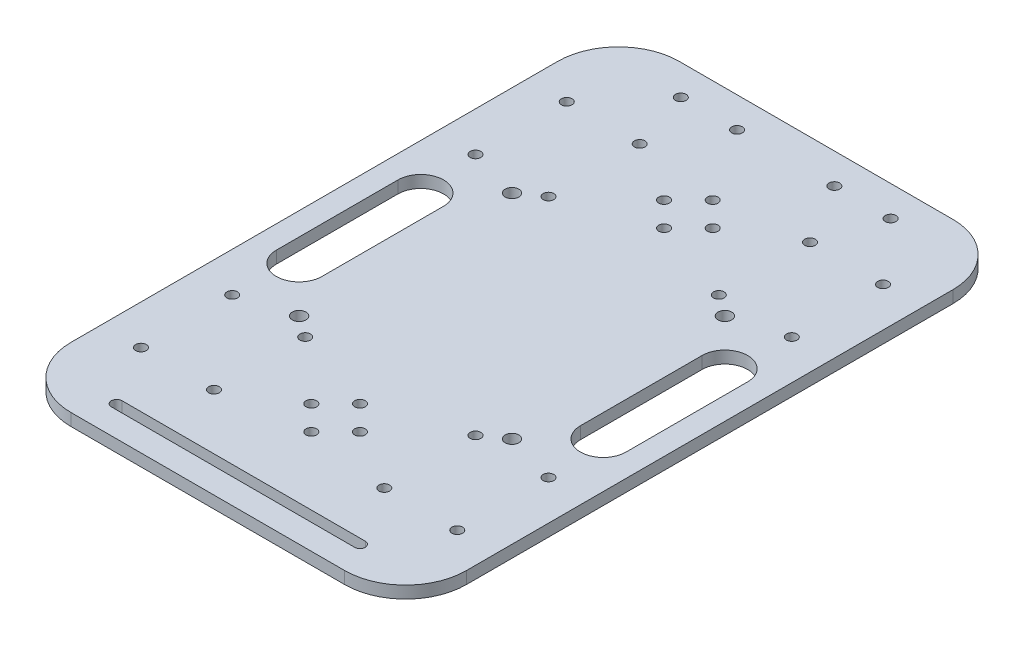
SolidWorks part; units mm, degrees
ref_plane "前视基准面" through (0, 0, 0) normal (0, 0, 1) x (1, 0, 0)
ref_plane "上视基准面" through (0, 0, 0) normal (0, 1, 0) x (1, 0, 0)
ref_plane "右视基准面" through (0, 0, 0) normal (1, 0, 0) x (0, 0, -1)
other "Configuration Table"
sketch "草图1" plane through (0, 0, 0) normal (0, 1, 0) x (1, 0, 0)
  line L0 (-40, -90) -> (40, -90) construction
  line L1 (-65, -100) -> (65, -100)
  line L2 (-65, -100) -> (-65, 100)
  line L3 (-65, 100) -> (65, 100)
  line L4 (65, -100) -> (65, 100)
  line L5 (-65, -100) -> (65, 100) construction
  line L6 (-65, 100) -> (65, -100) construction
  line L7 (-40, -88.25) -> (40, -88.25)
  line L8 (-40, -91.75) -> (40, -91.75)
  line L9 (50, -20) -> (50, 20) construction
  line L10 (42.5, -20) -> (42.5, 20)
  line L11 (57.5, -20) -> (57.5, 20)
  line L12 (-50, -20) -> (-50, 20) construction
  line L13 (-57.5, -20) -> (-57.5, 20)
  line L14 (-42.5, -20) -> (-42.5, 20)
  circle A0 centre (52, -70) radius 1.75
  circle A1 centre (52, -40) radius 1.75
  circle A2 centre (28, -40) radius 1.75
  circle A3 centre (28, -70) radius 1.75
  circle A4 centre (52, 40) radius 1.75
  circle A5 centre (52, 70) radius 1.75
  circle A6 centre (28, 70) radius 1.75
  circle A7 centre (28, 40) radius 1.75
  circle A8 centre (-28, 40) radius 1.75
  circle A9 centre (-28, 70) radius 1.75
  circle A10 centre (-52, 70) radius 1.75
  circle A11 centre (-52, 40) radius 1.75
  circle A12 centre (-28, -70) radius 1.75
  circle A13 centre (-28, -40) radius 1.75
  circle A14 centre (-52, -40) radius 1.75
  circle A15 centre (-52, -70) radius 1.75
  circle A16 centre (35, -35) radius 2.25
  circle A17 centre (-35, -35) radius 2.25
  circle A18 centre (-35, 35) radius 2.25
  circle A19 centre (35, 35) radius 2.25
  circle A20 centre (16, 90) radius 1.75
  circle A21 centre (-16, 90) radius 1.75
  circle A22 centre (-34.5, 90) radius 1.75
  circle A25 centre (34.5, 90) radius 1.75
  circle A26 centre (-8, 58) radius 1.75
  circle A29 centre (0, 50) radius 1.75
  circle A31 centre (0, 66) radius 1.75
  circle A33 centre (0, 0) radius 1.75
  circle A34 centre (8, 58) radius 1.75
  circle A35 centre (-8, -58) radius 1.75
  circle A36 centre (0, -66) radius 1.75
  circle A37 centre (0, -50) radius 1.75
  circle A38 centre (8, -58) radius 1.75
  arc A39 (-40, -88.25) -> (-40, -91.75) centre (-40, -90) ccw
  arc A40 (40, -91.75) -> (40, -88.25) centre (40, -90) ccw
  arc A41 (42.5, -20) -> (57.5, -20) centre (50, -20) ccw
  arc A42 (57.5, 20) -> (42.5, 20) centre (50, 20) ccw
  arc A43 (-57.5, -20) -> (-42.5, -20) centre (-50, -20) ccw
  arc A44 (-42.5, 20) -> (-57.5, 20) centre (-50, 20) ccw
  point P0 (0, 0)
  point P77 (0, -90)
  point P91 (50, 0)
  point P99 (-50, 0)
  dimension "D3" = 3.5
  dimension "D4" = 3.5
  dimension "D5" = 3.5
  dimension "D6" = 3.5
  dimension "D12" = 4.5
  dimension "D24" = 3.5
  dimension "D25" = 3.5
  dimension "D26" = 3.5
  dimension "D27" = 3.5
  dimension "D32" = 3.5
  dimension "D33" = 3.5
  dimension "D34" = 3.5
  dimension "D35" = 3.5
  dimension "D40" = 4.5
  dimension "D41" = 4.5
  dimension "D42" = 4.5
  dimension "D43" = 3.5
  dimension "D44" = 3.5
  dimension "D45" = 3.5
  dimension "D46" = 3.5
  dimension "D63" = 3.5
  dimension "D64" = 3.5
  dimension "D65" = 3.5
  dimension "D66" = 3.5
  dimension "D75" = 3.5
  dimension "D76" = 3.5
  dimension "D77" = 3.5
  dimension "D78" = 3.5
  dimension "D87" = 3.5
  dimension "D88" = 3.5
  dimension "D89" = 3.5
  dimension "D90" = 3.5
  dimension "D102" = 80
  dimension "D1" = 130
  dimension "D2" = 200
  dimension "D7" = 24
  dimension "D8" = 24
  dimension "D9" = 30
  dimension "D10" = 30
  dimension "D11" = 13
  dimension "D13" = 70
  dimension "D14" = 70
  dimension "D15" = 70
  dimension "D16" = 70
  dimension "D17" = 30
  dimension "D18" = 0
  dimension "D19" = 0
  dimension "D20" = 30
  dimension "D21" = 13
  dimension "D22" = 0
  dimension "D23" = 24
  dimension "D28" = 0
  dimension "D29" = 0
  dimension "D30" = 30
  dimension "D31" = 0
  dimension "D36" = 35
  dimension "D37" = 0
  dimension "D38" = 35
  dimension "D39" = 0
  dimension "D47" = 24
  dimension "D48" = 30
  dimension "D49" = 30
  dimension "D50" = 13
  dimension "D51" = 0
  dimension "D52" = 0
  dimension "D53" = 0
  dimension "D54" = 0
  dimension "D55" = 30
  dimension "D56" = 13
  dimension "D57" = 0
  dimension "D58" = 24
  dimension "D59" = 30
  dimension "D60" = 0
  dimension "D61" = 0
  dimension "D62" = 0
  dimension "D67" = 32
  dimension "D68" = 69
  dimension "D69" = 10
  dimension "D70" = 10
  dimension "D71" = 16
  dimension "D72" = 34.5
  dimension "D73" = 0
  dimension "D74" = 0
  dimension "D79" = 16
  dimension "D80" = 16
  dimension "D81" = 0
  dimension "D82" = 0
  dimension "D83" = 8
  dimension "D84" = 8
  dimension "D85" = 50
  dimension "D86" = 8
  dimension "D91" = 16
  dimension "D92" = 16
  dimension "D93" = 8
  dimension "D94" = 8
  dimension "D95" = 0
  dimension "D96" = 8
  dimension "D97" = 50
  dimension "D98" = 0
  dimension "D99" = 3.5
  dimension "D100" = 0
  dimension "D101" = 10
  dimension "D103" = 0
  dimension "D104" = 40
  dimension "D105" = 15
  dimension "D106" = 15
  dimension "D107" = 0
  dimension "D108" = 15
  dimension "D109" = 40
  dimension "D110" = 15
extrude "凸台-拉伸2" add sketch "草图1" along normal blind 4 contours L11 A42 L10 A41 | L14 A44 L13 A43 | L2 L1 L4 L3 | A11 | A18 | A8 | A10 | A9 | A22 | A21 | A20 | A25 | A6 | A31 | A26 | A34 | A29 | A5 | A4 | A7 | A19 | A1 | A16 | A2 | A0 | A3 | A37 | A35 | A38 | A36 | A13 | A17 | A14 | A15 | A12 | L7 A40 L8 A39 region at (50, 0, 0) region at (-50, 0, 0)
fillet "圆角1" radius 20 1 edges at (65, 2, 100)
fillet "圆角2" radius 20 1 edges at (-65, 2, 100)
fillet "圆角3" radius 20 1 edges at (-65, 2, -100)
fillet "圆角4" radius 20 1 edges at (65, 2, -100)
